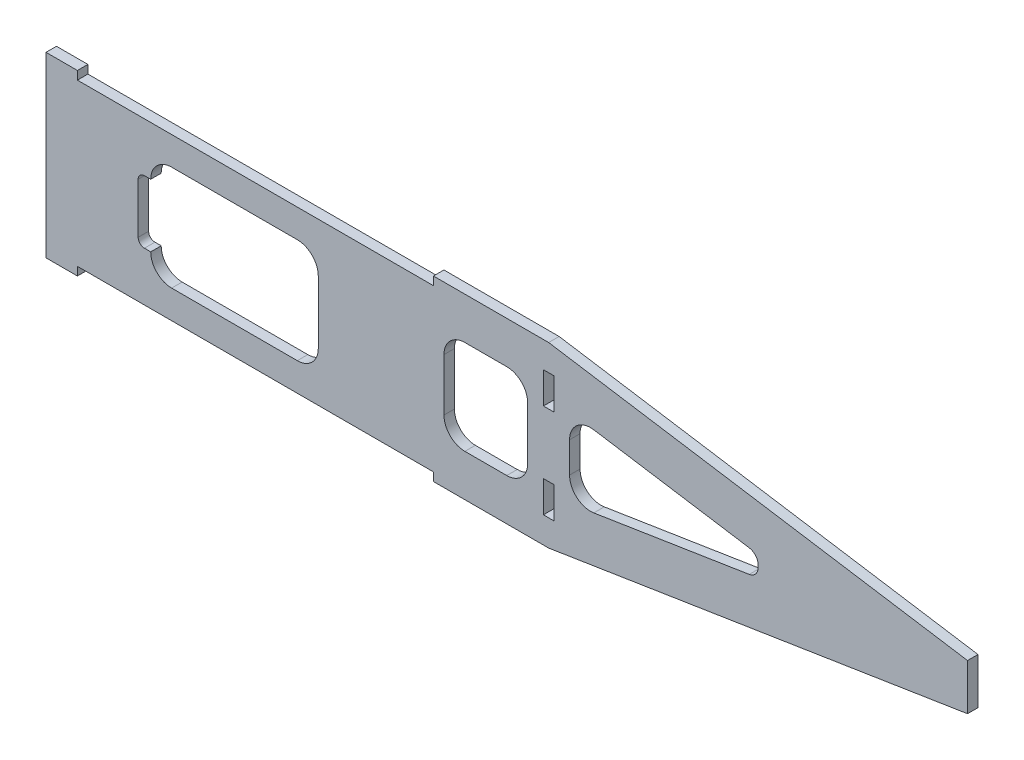
SolidWorks part; units mm, degrees
ref_plane "Ebene vorne" through (0, 0, 0) normal (0, 0, 1) x (1, 0, 0)
ref_plane "Ebene oben" through (0, 0, 0) normal (0, 1, 0) x (1, 0, 0)
ref_plane "Ebene rechts" through (0, 0, 0) normal (1, 0, 0) x (0, 0, -1)
sketch "Skizze1" plane through (0, 0, 0) normal (0, 0, 1) x (1, 0, 0)
  line L0 (0, 0) -> (440, 0) construction
  line L1 (0, 42.5) -> (0, -42.5)
  line L2 (0, -42.5) -> (240, -42.5)
  line L3 (240, -42.5) -> (440, -11)
  line L4 (440, -11) -> (440, 11)
  line L5 (240, 42.5) -> (440, 11)
  line L6 (0, 42.5) -> (240, 42.5)
  dimension "D1" = 440
  dimension "D2" = 85
  dimension "D3" = 22
  dimension "D4" = 200
extrude "Grundplatte" add sketch "Skizze1" along normal blind 5
sketch "Skizze2" plane through (0, 0, 5) normal (0, 0, 1) x (1, 0, 0)
  line L0 (50, 0) -> (44, 0) construction
  line L1 (130, 25) -> (50, 25)
  line L2 (130, 25) -> (130, -25)
  line L3 (130, -25) -> (50, -25)
  line L4 (50, 25) -> (50, 15)
  line L5 (130, 25) -> (50, -25) construction
  line L6 (130, -25) -> (50, 25) construction
  line L7 (44, -15) -> (44, 15)
  line L8 (44, 15) -> (50, 15)
  line L9 (44, -15) -> (50, -15)
  line L10 (50, -15) -> (50, -25)
  point P0 (90, 0)
  dimension "D1" = 90
  dimension "D2" = 50
  dimension "D3" = 80
  dimension "D4" = 30
  dimension "D5" = 6
extrude "Schnitt-Linear austragen1" cut sketch "Skizze2" against normal through all
fillet "Verrundung1" radius 10 4 edges at (130, 25, 2.5) (130, -25, 2.5) (50, 25, 2.5) (50, -25, 2.5)
sketch "Skizze3" plane through (0, 0, 5) normal (0, 0, 1) x (1, 0, 0)
  line L0 (0, 0) -> (440, 0) construction
  line L1 (0, 42.5) -> (0, -42.5) construction
  line L2 (440, -11) -> (440, 11) construction
  line L3 (240, 42.5) -> (0, 42.5) construction
  line L4 (15, 42.5) -> (185, 42.5)
  line L5 (15, 42.5) -> (15, 38.5)
  line L6 (15, 38.5) -> (185, 38.5)
  line L7 (185, 42.5) -> (185, 38.5)
  line L8 (185, -42.5) -> (185, -38.5)
  line L9 (15, -38.5) -> (185, -38.5)
  line L10 (15, -42.5) -> (15, -38.5)
  line L11 (15, -42.5) -> (185, -42.5)
  dimension "D1" = 4
  dimension "D2" = 170
  dimension "D3" = 15
extrude "Ausschnitt_Flächenaufdoppler" cut sketch "Skizze3" against normal through all
sketch "Skizze4" plane through (0, 0, 5) normal (0, 0, 1) x (1, 0, 0)
  line L0 (0, 0) -> (440, 0) construction
  line L1 (440, -11) -> (440, 11) construction
  line L2 (190, -22.5) -> (190, 22.5)
  line L3 (190, 22.5) -> (230, 22.5)
  line L4 (230, 22.5) -> (230, -22.5)
  line L6 (250, -19) -> (250, 19)
  line L7 (250, 19) -> (340, 4.825)
  line L8 (340, 4.825) -> (340, -4.825)
  line L9 (250, -19) -> (340, -4.825)
  line L10 (190, -22.5) -> (230, -22.5)
  line L11 (440, 11) -> (240, 42.5) construction
  line L13 (0, 42.5) -> (0, -42.5) construction
  point P14 (340, 0)
  point P17 (190, 0)
  dimension "D1" = 45
  dimension "D2" = 38
  dimension "D3" = 90
  dimension "D4" = 20
  dimension "D5" = 40
  dimension "D6" = 190
extrude "Ausschnitt Gewicht" cut sketch "Skizze4" against normal through all
fillet "Verrundung2" radius 10 6 edges at (250, -19, 2.5) (250, 19, 2.5) (190, -22.5, 2.5) (230, -22.5, 2.5) (230, 22.5, 2.5) (190, 22.5, 2.5)
fillet "Verrundung3" radius 5 2 edges at (340, -4.825, 2.5) (340, 4.825, 2.5)
fillet "Verrundung4" radius 3 2 edges at (44, -15, 2.5) (44, 15, 2.5)
sketch "Skizze5" plane through (0, 0, 5) normal (0, 0, 1) x (1, 0, 0)
  line L0 (240, 42.5) -> (240, 22.5) construction
  line L1 (240, 22.5) -> (240, -22.5) construction
  line L2 (240, -22.5) -> (240, -42.5) construction
  line L4 (242.5, 30) -> (237.5, 30)
  line L5 (242.5, 30) -> (242.5, 15)
  line L6 (242.5, 15) -> (237.5, 15)
  line L7 (237.5, 30) -> (237.5, 15)
  line L8 (242.5, 30) -> (237.5, 15) construction
  line L9 (242.5, 15) -> (237.5, 30) construction
  line L10 (242.5, -15) -> (237.5, -15)
  line L11 (242.5, -15) -> (242.5, -30)
  line L12 (242.5, -30) -> (237.5, -30)
  line L13 (237.5, -15) -> (237.5, -30)
  line L14 (242.5, -15) -> (237.5, -30) construction
  line L15 (242.5, -30) -> (237.5, -15) construction
  dimension "D1" = 30
  dimension "D2" = 5
  dimension "D3" = 15
extrude "Schnitt-Linear austragen2" cut sketch "Skizze5" against normal through all
